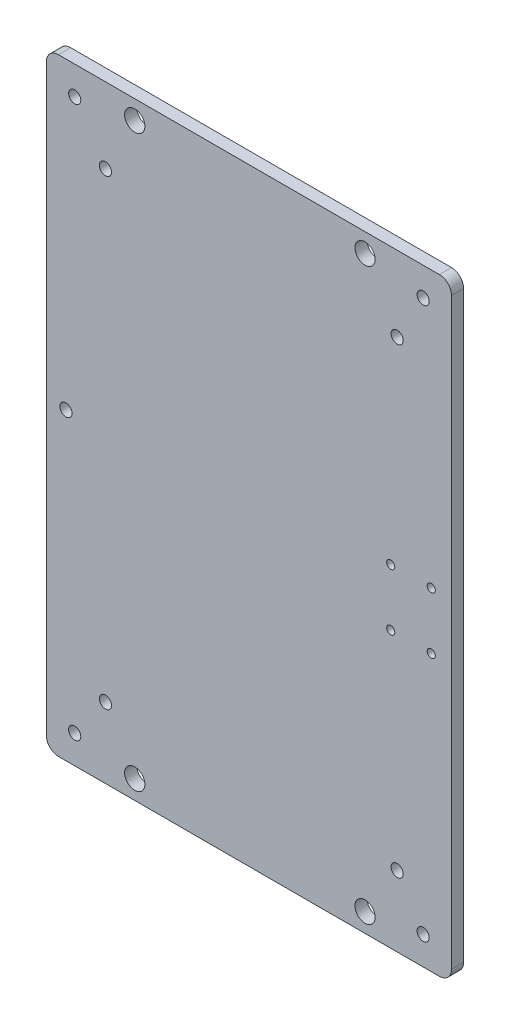
SolidWorks part; units mm, degrees
ref_plane "前视基准面" through (0, 0, 0) normal (0, 0, 1) x (1, 0, 0)
ref_plane "上视基准面" through (0, 0, 0) normal (0, 1, 0) x (1, 0, 0)
ref_plane "右视基准面" through (0, 0, 0) normal (1, 0, 0) x (0, 0, -1)
sketch "草图1" plane through (0, 0, 0) normal (0, 0, 1) x (1, 0, 0)
  line L0 (-102, -62) -> (-8, -62)
  line L1 (-5, -59) -> (-5, 85)
  line L2 (-8, 88) -> (-102, 88)
  line L3 (-105, 85) -> (-105, -59)
  circle A0 centre (-100.157, 13) radius 1.5
  circle A1 centre (-12, 81) radius 1.5
  circle A2 centre (-98, -55) radius 1.5
  circle A3 centre (-98, 81) radius 1.5
  circle A4 centre (-12, -55) radius 1.5
  circle A5 centre (-10, 6) radius 1
  circle A6 centre (-20, 20) radius 1
  circle A7 centre (-20, 6) radius 1
  circle A8 centre (-10, 20) radius 1
  arc A9 (-8, -62) -> (-5, -59) centre (-8, -59) ccw
  arc A10 (-5, 85) -> (-8, 88) centre (-8, 85) ccw
  arc A11 (-102, 88) -> (-105, 85) centre (-102, 85) ccw
  arc A12 (-105, -59) -> (-102, -62) centre (-102, -59) ccw
extrude "凸台-拉伸1" add sketch "草图1" against normal blind 3
sketch "草图2" plane through (0, 0, 0) normal (0, 0, 1) x (1, 0, 0)
  line L0 (-8, 88) -> (-102, 88) construction
  line L1 (-90.41, 69.42) -> (-18.41, 69.42)
  line L2 (-90.41, 69.42) -> (-90.41, -44.58)
  line L3 (-90.41, -44.58) -> (-18.41, -44.58)
  line L4 (-18.41, 69.42) -> (-18.41, -44.58)
  line L5 (-94.4101, 77.4226) -> (-14.4101, 77.4226)
  line L6 (-94.4101, 77.4226) -> (-94.4101, -52.5774)
  line L7 (-94.4101, -52.5774) -> (-14.4101, -52.5774)
  line L8 (-14.4101, 77.4226) -> (-14.4101, -52.5774)
  circle A0 centre (-90.41, 69.42) radius 1.5
  circle A1 centre (-18.41, 69.42) radius 1.5
  circle A2 centre (-90.41, -44.58) radius 1.5
  circle A3 centre (-18.41, -44.58) radius 1.5
  circle A4 centre (-83.1786, -57.3266) radius 2.5
  circle A5 centre (-26.3347, -57.3266) radius 2.5
  circle A6 centre (-83.1786, 83.33) radius 2.5
  circle A7 centre (-26.3347, 83.33) radius 2.5
  dimension "D3" = 4.67
  dimension "D1" = 114
  dimension "D2" = 72
extrude "切除-拉伸2" cut sketch "草图2" against normal blind 10 contours A2 | A3 | A1 | A0
extrude "切除-拉伸3" cut sketch "草图2<6>" against normal blind 10 contours A5 | A4
sketch "草图2<6>" plane through (0, 0, 0) normal (0, 0, 1) x (1, 0, 0) same geometry as "草图2"
extrude "切除-拉伸4" cut sketch "草图2<7>" against normal blind 10 contours A7 | A6
sketch "草图2<7>" plane through (0, 0, 0) normal (0, 0, 1) x (1, 0, 0) same geometry as "草图2"
